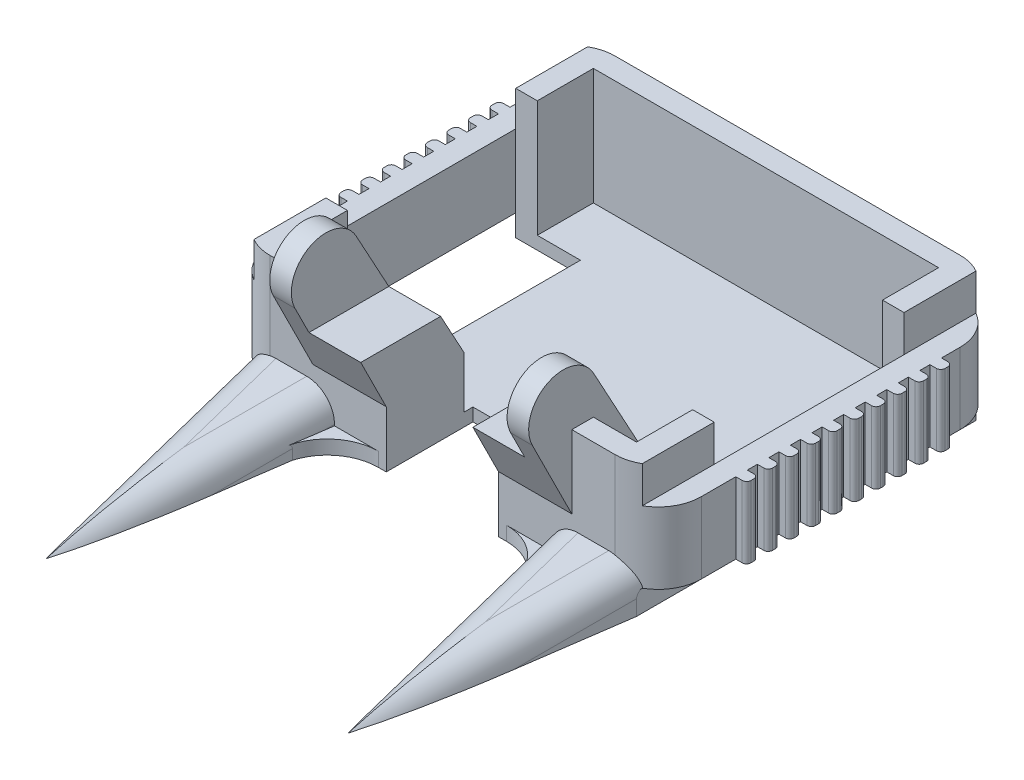
SolidWorks part; units mm, degrees
ref_plane "Front Plane" through (0, 0, 0) normal (0, 0, 1) x (1, 0, 0)
ref_plane "Top Plane" through (0, 0, 0) normal (0, 1, 0) x (1, 0, 0)
ref_plane "Right Plane" through (0, 0, 0) normal (1, 0, 0) x (0, 0, -1)
sketch "Sketch1" plane through (0, 0, 0) normal (0, 1, 0) x (1, 0, 0)
  line L0 (0, 99.9139) -> (0, -80.6698) construction
  line L1 (-45, 40) -> (45, 40)
  line L2 (-45, 40) -> (-45, -40)
  line L4 (45, 40) -> (45, -40)
  line L5 (-45, 40) -> (45, -40) construction
  line L6 (0, 0) -> (45, 40) construction
  line L7 (-35, -40) -> (-35, -110) construction
  line L8 (-45, -40) -> (-35, -110)
  line L9 (-25, -40) -> (-35, -110)
  line L10 (45, -40) -> (35, -110)
  line L11 (25, -40) -> (35, -110)
  line L12 (-25, -40) -> (25, -40)
  point P0 (0, 0)
  dimension "D1" = 80
  dimension "D2" = 90
  dimension "D3" = 10
  dimension "D4" = 70
  dimension "D5" = 70.7107
extrude "Boss-Extrude1" add sketch "Sketch1" along normal blind 30
sketch "Sketch2" plane through (0, 0, 0) normal (1, 0, 0) x (0, 0, -1)
  line L1 (-40, 30) -> (-40, 0) construction
  line L2 (-40, 15) -> (-40, 30)
  line L3 (-40, 30) -> (-110, 30)
  line L4 (-110, 30) -> (-110, 0)
  line L5 (-110, 0) -> (-40, 9.9928)
  line L6 (-40, 9.9928) -> (-40, 15)
  dimension "D1" = 15
extrude "Cut-Extrude1" cut sketch "Sketch2" against normal blind 45 and the other way blind 45
fillet "Fillet1" radius 10 rebuild error yes
sketch "Sketch3" plane through (0, 0, 0) normal (0, 1, 0) x (1, 0, 0)
  line L0 (-25, -40) -> (-28.384, -63.6881) construction
  line L1 (-45, -40) -> (45, -40) construction
  line L2 (-26.692, -51.8441) -> (-26.692, -40)
  line L3 (-26.692, -40) -> (-14.8529, -40)
  line L4 (0, 0) -> (0, -74.7886) construction
  line L5 (26.692, -51.8441) -> (26.692, -40)
  line L6 (26.692, -40) -> (14.8529, -40)
  arc A0 (-26.692, -51.8441) -> (-14.8529, -40) centre (-14.8504, -51.8416) cw
  arc A1 (26.692, -51.8441) -> (14.8529, -40) centre (14.8504, -51.8416) ccw
extrude "Boss-Extrude2" add sketch "Sketch3" along normal blind 3.25
sketch "Sketch4" plane through (0, 30, 0) normal (0, 1, 0) x (1, 0, 0)
  line L1 (-40, 35) -> (40, 35)
  line L2 (-40, 35) -> (-40, -35)
  line L3 (-40, -35) -> (40, -35)
  line L4 (40, 35) -> (40, -35)
  line L5 (-40, 35) -> (40, -35) construction
  line L6 (-40, -35) -> (40, 35) construction
  point P0 (0, 0)
  dimension "D1" = 80
  dimension "D2" = 70
extrude "Cut-Extrude2" cut sketch "Sketch4" against normal blind 27
sketch "Sketch5" plane through (0, 0, 0) normal (0, 1, 0) x (1, 0, 0)
  line L0 (0, 40) -> (0, -40) construction
  line L1 (45, 40) -> (-45, 40) construction
  line L2 (-45, -40) -> (45, -40) construction
  line L3 (-45, 40) -> (-45, -40) construction
  line L4 (-45, 22) -> (-30, 22)
  line L5 (-45, 22) -> (-45, -22)
  line L6 (-45, -22) -> (-30, -22)
  line L7 (-30, 22) -> (-30, -22)
  line L8 (45, 22) -> (30, 22)
  line L9 (45, 22) -> (45, -22)
  line L10 (45, -22) -> (30, -22)
  line L11 (30, 22) -> (30, -22)
  dimension "D1" = 18
  dimension "D2" = 44
  dimension "D3" = 15
extrude "Cut-Extrude3" cut sketch "Sketch5" along normal blind 30 contours L5 L4 L7 L6 | L8 L11 L10 L9
sketch "Sketch7" plane through (0, 0, 0) normal (1, 0, 0) x (0, 0, -1)
  line L0 (-22, 0) -> (-22, 15)
  line L1 (-22, 30) -> (-22, 0) construction
  line L5 (-40, 15) -> (-40, 5.076) construction
  line L6 (-40, 13.0839) -> (-40, 0)
  line L7 (-40, 0) -> (-22, 0)
  line L8 (-22, 15) -> (-34.9741, 38.8259)
  line L9 (-40, 13.0839) -> (-49.1576, 31.4266)
  arc A0 (-34.9741, 38.8259) -> (-49.1576, 31.4266) centre (-42, 35) ccw
  dimension "D1" = 16
  dimension "D2" = 35
  dimension "D3" = 2
  dimension "D4" = 20.5016
extrude "Boss-Extrude3" add sketch "Sketch7" along normal blind 30 and the other way blind 30
sketch "Sketch8" plane through (0, 0, 0) normal (1, 0, 0) x (0, 0, -1)
  line L0 (-22, 30) -> (-22, 0) construction
  line L1 (-55.2248, 45.2873) -> (-22, 45.2873)
  line L2 (-55.2248, 45.2873) -> (-55.2248, 24.935)
  line L3 (-55.2248, 24.935) -> (-22, 24.935)
  line L4 (-22, 45.2873) -> (-22, 24.935)
extrude "Cut-Extrude4" cut sketch "Sketch8" against normal blind 25 and the other way blind 25
sketch "Sketch9" plane through (0, 0, 0) normal (0, 1, 0) x (1, 0, 0)
  line L0 (25, -45.9166) -> (-25, -45.9166) construction
  line L1 (-13, -19.9166) -> (13, -19.9166)
  line L2 (-13, -19.9166) -> (-13, -45.9166)
  line L3 (-13, -45.9166) -> (13, -45.9166)
  line L4 (13, -19.9166) -> (13, -45.9166)
  line L5 (-13, -19.9166) -> (13, -45.9166) construction
  line L6 (-13, -45.9166) -> (13, -19.9166) construction
  point P0 (0, -32.9166)
  dimension "D1" = 26
  dimension "D2" = 0
  dimension "D3" = 26
extrude "Cut-Extrude5" cut sketch "Sketch9" along normal blind 25
sketch "Sketch10" plane through (45, 0, 0) normal (1, 0, 0) x (0, 0, -1)
  line L0 (-40, 30) -> (-40, 13.0839) construction
  line L1 (-40, 21.542) -> (40, 21.542)
  line L2 (-40, 21.542) -> (-40, 5)
  line L3 (-40, 5) -> (40, 5)
  line L4 (40, 21.542) -> (40, 5)
  line L5 (40, 30) -> (40, 0) construction
  line L6 (-40, 0) -> (-22, 0) construction
  dimension "D1" = 5
  dimension "D2" = 16.542
  dimension "D3" = 80
extrude "Boss-Extrude4" add sketch "Sketch10" along normal blind 5
fillet "Fillet6" radius 10 2 edges at (50, 13.271, -40) (50, 13.271, 40)
sketch "Sketch11" plane through (50, 0, 0) normal (1, 0, 0) x (0, 0, -1)
  line L0 (-30, 5) -> (30, 5) construction
  line L1 (-22, 21.542) -> (-19.3292, 21.542)
  line L2 (-22, 21.542) -> (-22, 5)
  line L3 (-22, 5) -> (-19.3292, 5)
  line L4 (-19.3292, 21.542) -> (-19.3292, 5)
  line L5 (-17, 21.542) -> (-17, 5)
  line L6 (-17, 21.542) -> (-14.3292, 21.542)
  line L7 (-14.3292, 21.542) -> (-14.3292, 5)
  line L8 (-17, 5) -> (-14.3292, 5)
  line L9 (-12, 21.542) -> (-12, 5)
  line L10 (-12, 21.542) -> (-9.3292, 21.542)
  line L11 (-9.3292, 21.542) -> (-9.3292, 5)
  line L12 (-12, 5) -> (-9.3292, 5)
  line L13 (-7, 21.542) -> (-7, 5)
  line L14 (-7, 21.542) -> (-4.3292, 21.542)
  line L15 (-4.3292, 21.542) -> (-4.3292, 5)
  line L16 (-7, 5) -> (-4.3292, 5)
  line L17 (-2, 21.542) -> (-2, 5)
  line L18 (-2, 21.542) -> (0.6708, 21.542)
  line L19 (0.6708, 21.542) -> (0.6708, 5)
  line L20 (-2, 5) -> (0.6708, 5)
  line L21 (3, 21.542) -> (3, 5)
  line L22 (3, 21.542) -> (5.6708, 21.542)
  line L23 (5.6708, 21.542) -> (5.6708, 5)
  line L24 (3, 5) -> (5.6708, 5)
  line L25 (8, 21.542) -> (8, 5)
  line L26 (8, 21.542) -> (10.6708, 21.542)
  line L27 (10.6708, 21.542) -> (10.6708, 5)
  line L28 (8, 5) -> (10.6708, 5)
  line L29 (13, 21.542) -> (13, 5)
  line L30 (13, 21.542) -> (15.6708, 21.542)
  line L31 (15.6708, 21.542) -> (15.6708, 5)
  line L32 (13, 5) -> (15.6708, 5)
  line L33 (18, 21.542) -> (18, 5)
  line L34 (18, 21.542) -> (20.6708, 21.542)
  line L35 (20.6708, 21.542) -> (20.6708, 5)
  line L36 (18, 5) -> (20.6708, 5)
  line L37 (23, 21.542) -> (23, 5)
  line L38 (23, 21.542) -> (25.6708, 21.542)
  line L39 (25.6708, 21.542) -> (25.6708, 5)
  line L40 (23, 5) -> (25.6708, 5)
  dimension "D1" = 10
extrude "Boss-Extrude5" add sketch "Sketch11" along normal blind 2.5
fillet "Fillet8" radius 1 20 edges at (52.5, 13.271, -8) (52.5, 13.271, -10.6708) (52.5, 13.271, -13) (52.5, 13.271, -15.6708) (52.5, 13.271, -18) (52.5, 13.271, -20.6708) (52.5, 13.271, -23) (52.5, 13.271, -25.6708) (52.5, 13.271, -5.6708) (52.5, 13.271, -3) (52.5, 13.271, -0.6708) (52.5, 13.271, 2) (52.5, 13.271, 4.3292) (52.5, 13.271, 7) (52.5, 13.271, 9.3292) (52.5, 13.271, 12) (52.5, 13.271, 14.3292) (52.5, 13.271, 17) (52.5, 13.271, 19.3292) (52.5, 13.271, 22)
sketch "Sketch12" plane through (0, 0, -40) normal (0, 0, -1) x (-1, 0, 0)
  line L0 (-23.9219, 21.7959) -> (-22.0999, 21.7959)
  line L1 (-23.9219, 5.333) -> (-22.0999, 5.333)
  line L3 (-36.4805, 21.7959) -> (-33.7476, 21.7959)
  line L6 (-36.4805, 21.7959) -> (-31.0146, 5.333)
  line L7 (-31.0146, 5.333) -> (-25.4836, 21.7959)
  line L8 (-25.4836, 21.7959) -> (-28.2491, 21.7959)
  line L9 (-28.2491, 21.7959) -> (-31.0146, 13.5645)
  line L10 (-31.0146, 13.5645) -> (-33.7476, 21.7959)
  line L11 (-33.7476, 21.7959) -> (-36.4805, 21.7959)
  line L12 (-36.4805, 21.7959) -> (-33.7476, 21.7959)
  line L13 (-23.9219, 21.7959) -> (-23.9219, 5.333)
  line L14 (-23.9219, 5.333) -> (-22.0999, 5.333)
  line L15 (-22.0999, 5.333) -> (-22.0999, 21.7959)
  line L16 (-22.0999, 21.7959) -> (-23.9219, 21.7959)
  line L17 (-19.1717, 5.333) -> (-19.1717, 21.7959)
  line L18 (-19.1717, 21.7959) -> (-10.9728, 21.7959)
  line L19 (-10.9728, 21.7959) -> (-10.9728, 13.5645)
  line L20 (-10.9728, 13.5645) -> (-16.3737, 13.5645)
  line L21 (-16.3737, 13.5645) -> (-16.3737, 5.333)
  line L22 (-16.3737, 5.333) -> (-19.1717, 5.333)
  line L23 (-8.5002, 21.7959) -> (-8.5002, 5.333)
  line L24 (-8.5002, 5.333) -> (-2.839, 5.333)
  line L25 (-2.839, 5.333) -> (-2.839, 8.6516)
  line L26 (-2.839, 8.6516) -> (-6.9385, 8.6516)
  line L27 (-6.9385, 8.6516) -> (-6.9385, 12.686)
  line L28 (-6.9385, 12.686) -> (-2.839, 12.686)
  line L29 (-2.839, 12.686) -> (-3.6849, 15.2888)
  line L30 (-3.6849, 15.2888) -> (-6.9385, 15.2888)
  line L31 (-6.9385, 15.2888) -> (-6.9385, 19.5184)
  line L32 (-6.9385, 19.5184) -> (-2.839, 19.5184)
  line L33 (-2.839, 19.5184) -> (-2.839, 21.7959)
  line L34 (-2.839, 21.7959) -> (-8.5002, 21.7959)
  line L35 (0, 5.333) -> (0, 21.7959)
  line L36 (0, 21.7959) -> (8.757, 21.7959)
  line L37 (8.757, 21.7959) -> (8.757, 18.1999)
  line L38 (8.757, 18.1999) -> (6.077, 18.1999)
  line L39 (6.077, 18.1999) -> (16.8774, 5.333)
  line L40 (16.8774, 5.333) -> (12.2574, 5.333)
  line L41 (12.2574, 5.333) -> (7.1726, 11.3907)
  line L42 (7.1726, 11.3907) -> (6.9927, 5.333)
  line L43 (6.9927, 5.333) -> (0, 5.333)
  line L44 (-28.2491, 21.7959) -> (-25.4836, 21.7959)
  line L45 (-28.2491, 21.7959) -> (-25.4836, 21.7959)
  line L46 (-19.1717, 21.7959) -> (-10.9728, 21.7959)
  line L47 (-19.1717, 5.333) -> (-16.3737, 5.333)
  line L48 (-8.5002, 5.333) -> (-2.839, 5.333)
  line L49 (-8.5002, 21.7959) -> (-2.839, 21.7959)
  line L50 (0, 5.333) -> (6.9927, 5.333)
  line L51 (0, 21.7959) -> (8.757, 21.7959)
  line L52 (12.2574, 5.333) -> (16.8774, 5.333)
sketch "Sketch13" plane through (-45, 0, 0) normal (-1, 0, 0) x (0, 0, 1)
  line L0 (-40, 30) -> (-40, 0) construction
  line L1 (-40, 5) -> (40, 5)
  line L2 (-40, 5) -> (-40, 21.87)
  line L3 (-40, 21.87) -> (40, 21.87)
  line L4 (40, 5) -> (40, 21.87)
  line L5 (40, 30) -> (40, 13.0839) construction
  line L6 (-40, 0) -> (-22, 0) construction
  dimension "D1" = 5
  dimension "D2" = 16.87
extrude "Boss-Extrude6" add sketch "Sketch13" along normal blind 5
sketch "Sketch14" plane through (-50, 0, 0) normal (-1, 0, 0) x (0, 0, 1)
  line L0 (17, 21.87) -> (17, 5)
  line L1 (22, 21.87) -> (19.3292, 21.87)
  line L2 (22, 21.87) -> (22, 5)
  line L3 (22, 5) -> (19.3292, 5)
  line L4 (19.3292, 21.87) -> (19.3292, 5)
  line L5 (17, 21.87) -> (14.3292, 21.87)
  line L6 (14.3292, 21.87) -> (14.3292, 5)
  line L7 (17, 5) -> (14.3292, 5)
  line L8 (12, 21.87) -> (12, 5)
  line L9 (12, 21.87) -> (9.3292, 21.87)
  line L10 (9.3292, 21.87) -> (9.3292, 5)
  line L11 (12, 5) -> (9.3292, 5)
  line L12 (7, 21.87) -> (7, 5)
  line L13 (7, 21.87) -> (4.3292, 21.87)
  line L14 (4.3292, 21.87) -> (4.3292, 5)
  line L15 (7, 5) -> (4.3292, 5)
  line L16 (2, 21.87) -> (2, 5)
  line L17 (2, 21.87) -> (-0.6708, 21.87)
  line L18 (-0.6708, 21.87) -> (-0.6708, 5)
  line L19 (2, 5) -> (-0.6708, 5)
  line L20 (-3, 21.87) -> (-3, 5)
  line L21 (-3, 21.87) -> (-5.6708, 21.87)
  line L22 (-5.6708, 21.87) -> (-5.6708, 5)
  line L23 (-3, 5) -> (-5.6708, 5)
  line L24 (-8, 21.87) -> (-8, 5)
  line L25 (-8, 21.87) -> (-10.6708, 21.87)
  line L26 (-10.6708, 21.87) -> (-10.6708, 5)
  line L27 (-8, 5) -> (-10.6708, 5)
  line L28 (-13, 21.87) -> (-13, 5)
  line L29 (-13, 21.87) -> (-15.6708, 21.87)
  line L30 (-15.6708, 21.87) -> (-15.6708, 5)
  line L31 (-13, 5) -> (-15.6708, 5)
  line L32 (-18, 21.87) -> (-18, 5)
  line L33 (-18, 21.87) -> (-20.6708, 21.87)
  line L34 (-20.6708, 21.87) -> (-20.6708, 5)
  line L35 (-18, 5) -> (-20.6708, 5)
  line L36 (-23, 21.87) -> (-23, 5)
  line L37 (-23, 21.87) -> (-25.6708, 21.87)
  line L38 (-25.6708, 21.87) -> (-25.6708, 5)
  line L39 (-23, 5) -> (-25.6708, 5)
  dimension "D1" = 2.6708
  dimension "D2" = 10
extrude "Boss-Extrude7" add sketch "Sketch14" along normal blind 2.5
fillet "Fillet10" radius 1 20 edges at (-52.5, 13.435, 22) (-52.5, 13.435, 19.3292) (-52.5, 13.435, 17) (-52.5, 13.435, 14.3292) (-52.5, 13.435, 12) (-52.5, 13.435, 7) (-52.5, 13.435, 9.3292) (-52.5, 13.435, 4.3292) (-52.5, 13.435, 2) (-52.5, 13.435, -0.6708) (-52.5, 13.435, -3) (-52.5, 13.435, -5.6708) (-52.5, 13.435, -8) (-52.5, 13.435, -10.6708) (-52.5, 13.435, -13) (-52.5, 13.435, -15.6708) (-52.5, 13.435, -18) (-52.5, 13.435, -20.6708) (-52.5, 13.435, -23) (-52.5, 13.435, -25.6708)
fillet "Fillet11" radius 10 2 edges at (-50, 13.435, 40) (-50, 13.435, -40)
fillet "Fillet15" radius 6.5 4 edges at (40.1046, 5.1009, 74.268) (30, 4.9964, 75) (-30, 4.9964, 75) (-40.1046, 5.1009, 74.268)
